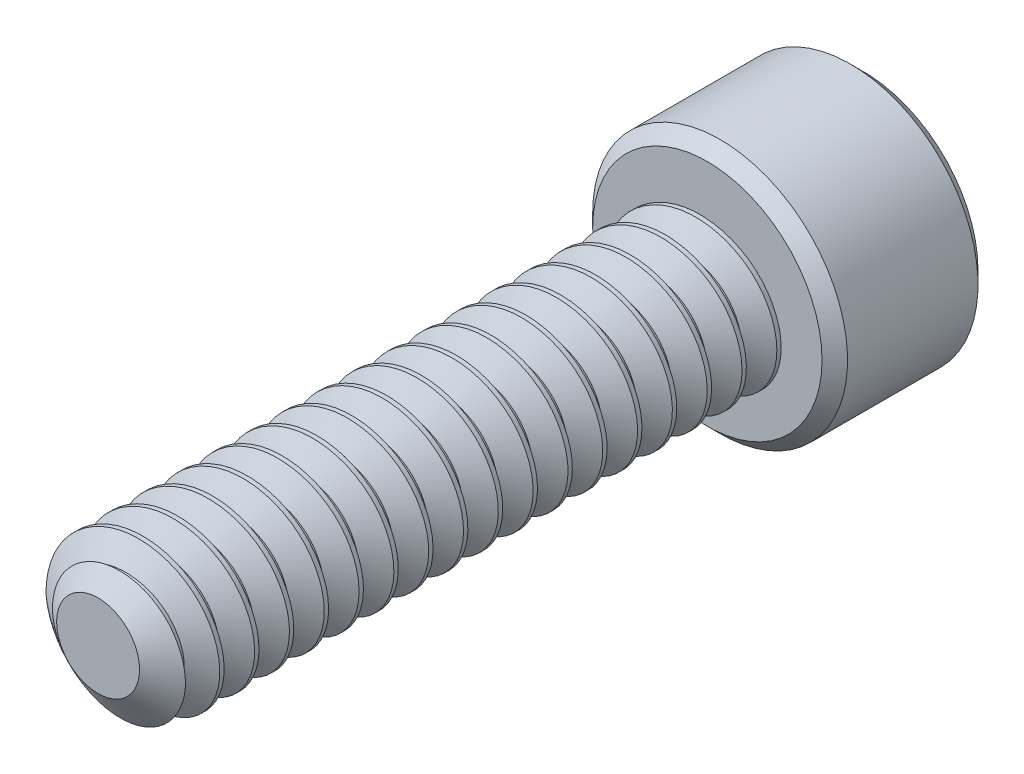
SolidWorks part; units mm, degrees
other "DetailItem1"
ref_plane "Front Plane" through (0, 0, 0) normal (0, 0, 1) x (1, 0, 0)
ref_plane "Top Plane" through (0, 0, 0) normal (0, 1, 0) x (1, 0, 0)
ref_plane "Right Plane" through (0, 0, 0) normal (1, 0, 0) x (0, 0, -1)
sketch "Sketch1" plane through (0, 0, 0) normal (0, 0, 1) x (1, 0, 0)
  circle A0 centre (0, 0) radius 1.4224
  dimension "OD" = 2.8448
extrude "Extrude1" add sketch "Sketch1" against normal blind 11.1125
sketch "Sketch2" plane through (0, 0, 0) normal (0, 0, 1) x (1, 0, 0)
  circle A0 centre (0, 0) radius 1.4224 construction
  circle A1 centre (0, 0) radius 1.4224
curve "Helix/Spiral1" pitch 0.635 height 11.7475 radius 1.4224 centre (0, 0, 0) axis (0, 0, -1) start towards (0, 1, 0) parameters "pitch"=0.635
sketch "Sketch3" plane through (0, 0, 0) normal (1, 0, 0) x (0, 0, -1)
  line L0 (-0.5556, 1.4224) -> (-0.3175, 1.01)
  line L1 (-0.3175, 1.01) -> (-0.2381, 1.01)
  line L2 (-0.2381, 1.01) -> (0, 1.4224)
  line L3 (-0.5556, 1.4224) -> (0, 1.4224)
  line L4 (-0.2778, 1.4224) -> (-0.2778, 1.01) construction
  line L5 (-0.4366, 1.2162) -> (-0.1191, 1.2162) construction
  line L6 (0, 1.4224) -> (0, -1.4224) construction
  dimension "D1" = 0.0794
  dimension "D2" = 0.3175
  dimension "D3" = 60
sweep "Cut-Sweep1" cut profiles "Sketch3" path "Helix/Spiral1"
sketch "Sketch4" plane through (0, 0, 0) normal (1, 0, 0) x (0, 0, -1)
  line L0 (0.4666, 1.4224) -> (0, 0.756)
  line L1 (0, 0.756) -> (0, 1.4224)
  line L2 (0.4666, 1.4224) -> (0, 1.4224)
  line L3 (-0.5556, 1.4224) -> (0, 1.4224) construction
  line L4 (0, 0) -> (7.0209, 0) construction
  dimension "D1" = 55
  dimension "D2" = 0.254
revolve "Cut-Revolve1" cut sketch "Sketch4" angle 360 about L4
sketch "Sketch5" plane through (0, 0, 0) normal (1, 0, 0) x (0, 0, -1)
  line L0 (11.1125, -1.0149) -> (11.1125, 1.0232) construction
  line L1 (11.1125, 1.5494) -> (0.1202, 1.5494)
  line L2 (11.1125, 1.5494) -> (11.1125, 0)
  line L3 (11.1125, 0) -> (0, 0)
  line L4 (0, 1.2192) -> (0, 0)
  line L5 (0.1202, 1.5494) -> (0, 1.2192)
  line L6 (0, 0) -> (9.9695, 0) construction
  point P3 (0, 1.5494)
  point P10 (0, 1.5494)
  dimension "D1" = 0.3302
  dimension "D2" = 0.127
  dimension "D3" = 20
  dimension "Min Thread" = 0
revolve "partially thread" [suppressed] add sketch "Sketch5" angle 360 about L6
sketch "Sketch6" plane through (0, 0, -11.1125) normal (0, 0, -1) x (-1, 0, 0)
  circle A0 centre (0, 0) radius 2.3241
  dimension "head dia" = 4.6482
extrude "Extrude2" add sketch "Sketch6" along normal blind 2.8448
sketch "Sketch7" plane through (0, 0, -13.9573) normal (0, 0, -1) x (-1, 0, 0)
  line L1 (0, 1.3748) -> (-1.1906, 0.6874)
  line L2 (-1.1906, 0.6874) -> (-1.1906, -0.6874)
  line L3 (-1.1906, -0.6874) -> (0, -1.3748)
  line L4 (0, -1.3748) -> (1.1906, -0.6874)
  line L5 (1.1906, -0.6874) -> (1.1906, 0.6874)
  line L6 (1.1906, 0.6874) -> (0, 1.3748)
  circle A0 centre (0, 0) radius 1.1906 construction
  dimension "hex dia" = 2.3813
extrude "Cut-Extrude1" cut sketch "Sketch7" against normal blind 1.7859
sketch "Sketch8" plane through (0, 0, -13.9573) normal (0, 0, -1) x (-1, 0, 0)
  circle A0 centre (0, 0) radius 1.3748
extrude "Cut-Extrude2" cut sketch "Sketch8" against normal through all draft 45
chamfer "Chamfer1" distance 0.2324 angle 45 2 edges at (-2.3241, 0, -13.9573) (-2.3241, 0, -11.1125)
sketch "Sketch9" plane through (0, 0, 0) normal (1, 0, 0) x (0, 0, -1)
  line L0 (0, 1.4224) -> (0, -1.4224) construction
  line L1 (1.5875, 1.4224) -> (1.5875, -1.4224) construction
  dimension "D1" = 1.5875
  dimension "D4" = 0.635
  dimension "D5" = 0.3302
equation "\"D3@Helix/Spiral1\" = \"screw length@Extrude1\"+\"pitch@Helix/Spiral1\""
equation "\"D1@Sketch3\" = \"pitch@Helix/Spiral1\"*.125"
equation "\"D2@Sketch3\" = \"pitch@Helix/Spiral1\"*.5"
equation "\"D1@Cut-Extrude1\" = \"hex dia@Sketch7\"*.75"
equation "\"D1@Chamfer1\" = \"head dia@Sketch6\"*.05"
equation "\"D1@Sketch9\" = \"pitch@Helix/Spiral1\"*2.5"
